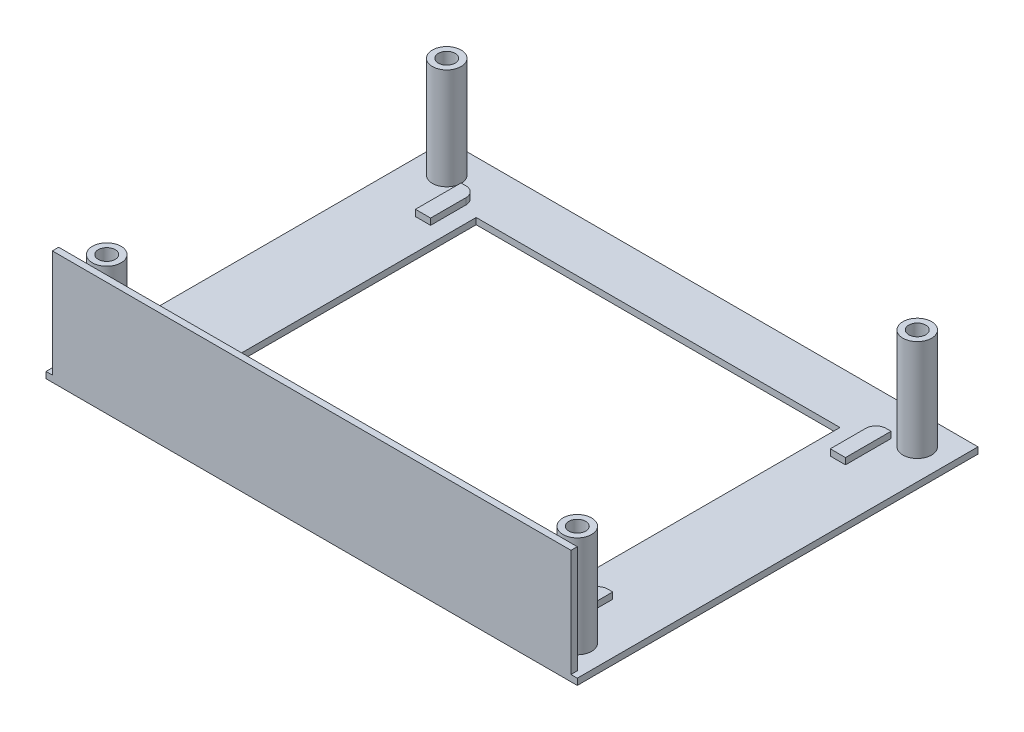
SolidWorks part; units mm, degrees
ref_plane "Front Plane" through (0, 0, 0) normal (0, 0, 1) x (1, 0, 0)
ref_plane "Top Plane" through (0, 0, 0) normal (0, 1, 0) x (1, 0, 0)
ref_plane "Right Plane" through (0, 0, 0) normal (1, 0, 0) x (0, 0, -1)
sketch "Sketch1" plane through (0, 0, 0) normal (0, 1, 0) x (1, 0, 0)
  line L1 (-45.6406, -34.1312) -> (45.6406, -34.1312)
  line L2 (-45.6406, -34.1312) -> (-45.6406, 34.1313)
  line L3 (-45.6406, 34.1313) -> (45.6406, 34.1313)
  line L4 (45.6406, -34.1312) -> (45.6406, 34.1313)
  line L5 (-45.6406, -34.1312) -> (45.6406, 34.1313) construction
  line L6 (-45.6406, 34.1313) -> (45.6406, -34.1312) construction
  line L7 (-49.6406, 38.1313) -> (50.6406, 38.1313)
  line L8 (-49.6406, 35.5913) -> (-49.6406, -43.1312)
  line L9 (-49.6406, -43.1312) -> (50.6406, -43.1312)
  line L10 (50.6406, -34.2413) -> (50.6406, -43.1312)
  line L11 (19.6844, -43.1312) -> (-7.5719, -43.1312)
  line L12 (19.6844, -43.1312) -> (19.6844, -49.4812)
  line L13 (19.6844, -49.4812) -> (-7.5719, -49.4812)
  line L14 (-7.5719, -43.1312) -> (-7.5719, -49.4812)
  line L15 (-66.1506, 47.2512) -> (67.1506, 47.2512)
  line L16 (-66.1506, 47.2512) -> (-66.1506, -53.2912)
  line L17 (-66.1506, -53.2912) -> (67.1506, -53.2912)
  line L18 (67.1506, 47.2512) -> (67.1506, -53.2912)
  line L19 (-52.1806, 38.1313) -> (-53.4506, 38.1313)
  line L20 (-49.6406, 38.1313) -> (-49.6406, 26.7013)
  line L21 (-49.6406, 26.7013) -> (-53.4506, 26.7013)
  line L22 (-53.4506, 38.1313) -> (-53.4506, 26.7013)
  line L23 (53.1806, 38.1313) -> (54.4506, 38.1313)
  line L24 (50.6406, 38.1313) -> (50.6406, 26.7013)
  line L25 (50.6406, 26.7013) -> (54.4506, 26.7013)
  line L26 (54.4506, 38.1313) -> (54.4506, 26.7013)
  line L27 (-49.6406, -43.1312) -> (-53.4506, -43.1312)
  line L28 (-49.6406, -43.1312) -> (-49.6406, -34.2413)
  line L29 (-52.1806, -31.7012) -> (-53.4506, -31.7012)
  line L30 (-53.4506, -43.1312) -> (-53.4506, -31.7012)
  line L31 (50.6406, -43.1312) -> (54.4506, -43.1312)
  line L32 (50.6406, -43.1312) -> (50.6406, -31.7012)
  line L33 (53.1806, -31.7012) -> (54.4506, -31.7012)
  line L34 (54.4506, -43.1312) -> (54.4506, -31.7012)
  line L35 (-53.4506, -46.9412) -> (-36.9406, -46.9412)
  line L36 (-53.4506, -46.9412) -> (-53.4506, -43.1312)
  line L37 (-53.4506, -43.1312) -> (-36.9406, -43.1312)
  line L38 (-36.9406, -46.9412) -> (-36.9406, -43.1312)
  line L39 (54.4506, -43.1312) -> (39.2106, -43.1312)
  line L40 (54.4506, -43.1312) -> (54.4506, -46.9412)
  line L41 (54.4506, -46.9412) -> (39.2106, -46.9412)
  line L42 (39.2106, -43.1312) -> (39.2106, -46.9412)
  line L43 (-66.1506, -53.2912) -> (67.1506, -53.2912)
  line L44 (-66.1506, -53.2912) -> (-66.1506, -51.7038)
  line L45 (-66.1506, -51.7038) -> (67.1506, -51.7038)
  line L46 (67.1506, -53.2912) -> (67.1506, -51.7038)
  line L47 (-66.1506, -51.7038) -> (-64.5631, -51.7038)
  line L48 (-66.1506, -51.7038) -> (-66.1506, -53.2912)
  line L49 (-66.1506, -53.2912) -> (-64.5631, -53.2913)
  line L50 (-64.5631, -51.7038) -> (-64.5631, -53.2913)
  line L51 (67.1506, -51.7038) -> (65.5631, -51.7038)
  line L52 (67.1506, -51.7038) -> (67.1506, -53.2912)
  line L53 (67.1506, -53.2912) -> (65.5631, -53.2913)
  line L54 (65.5631, -51.7038) -> (65.5631, -53.2913)
  arc A0 (-49.6406, 35.5913) -> (-52.1806, 38.1313) centre (-52.1806, 35.5913) ccw
  arc A1 (50.6406, 35.5912) -> (53.1806, 38.1313) centre (53.1806, 35.5913) cw
  arc A2 (50.6406, -34.2413) -> (53.1806, -31.7012) centre (53.1806, -34.2412) cw
  arc A3 (-49.6406, -34.2413) -> (-52.1806, -31.7012) centre (-52.1806, -34.2412) ccw
  circle A4 centre (59.5306, 39.6312) radius 3.6
  circle A5 centre (-58.5306, 39.6312) radius 3.6
  circle A6 centre (59.5306, -45.6712) radius 3.6
  circle A7 centre (-58.5306, -45.6713) radius 3.6
  circle A8 centre (-58.5306, 39.6312) radius 2.125
  circle A9 centre (59.5306, 39.6312) radius 2.125
  circle A10 centre (59.5306, -45.6712) radius 2.125
  circle A11 centre (-58.5306, -45.6713) radius 2.125
  point P0 (0, 0)
  point P14 (0, 0)
  point P48 (-49.6406, -31.7012)
  dimension "D24" = 2.54
  dimension "D25" = 2.54
  dimension "D20" = 2.54
  dimension "D26" = 2.54
  dimension "D27" = 7.62
  dimension "D35" = 1.5875
  dimension "D1" = 91.2812
  dimension "D2" = 68.2625
  dimension "D3" = 4
  dimension "D4" = 4
  dimension "D5" = 5
  dimension "D6" = 9
  dimension "D7" = 30.9562
  dimension "D8" = 42.0688
  dimension "D9" = 6.35
  dimension "D10" = 16.51
  dimension "D11" = 16.51
  dimension "D12" = 3.81
  dimension "D13" = 11.43
  dimension "D14" = 3.81
  dimension "D15" = 3.81
  dimension "D16" = 11.43
  dimension "D17" = 3.81
  dimension "D18" = 16.51
  dimension "D19" = 3.81
  dimension "D21" = 11.43
  dimension "D22" = 11.43
  dimension "D23" = 3.81
  dimension "D28" = 7.62
  dimension "D29" = 7.62
  dimension "D30" = 7.62
  dimension "D31" = 7.62
  dimension "D32" = 7.62
  dimension "D33" = 7.62
  dimension "D34" = 7.62
  dimension "D36" = 1.5875
  dimension "D37" = 1.5875
  dimension "D38" = 9.12
extrude "Boss-Extrude1" add sketch "Sketch1" against normal blind 1.5875 contours L17 L18 L15 L16
extrude "Boss-Extrude2" add sketch "Sketch1<3>" along normal blind 25.4 contours A5 A8 | A4 A9 | A6 A10 | A7 A11 region at (56.0324, 0, -39.6312) region at (-62.0288, 0, -39.6312) region at (56.0324, 0, 45.6712) region at (-62.0288, 0, 45.6713)
sketch "Sketch1<3>" plane through (0, 0, 0) normal (0, 1, 0) x (1, 0, 0) same geometry as "Sketch1"
extrude "Boss-Extrude4" add sketch "Sketch1<6>" along normal blind 1.5875 contours L8 A0 L19 L22 L21 | A1 L24 L25 L26 L23 | A2 L10 L31 L34 L33 | L9 L42 L41 L40 L31 | L35 L38 L9 L27 L36 | L8 A3 L29 L30 L27 region at (52.5895, 0, -32.2472) region at (46.8306, 0, 45.0362) region at (-51.5895, 0, 37.5853) region at (-51.5895, 0, -32.2472) region at (-45.1956, 0, 45.0362) region at (52.5895, 0, 37.5853)
sketch "Sketch1<6>" plane through (0, 0, 0) normal (0, 1, 0) x (1, 0, 0) same geometry as "Sketch1"
extrude "Cut-Extrude1" cut sketch "Sketch1<7>" against normal blind 4.1275 contours L1 L4 L3 L2 region at (0, 0, 0)
sketch "Sketch1<7>" plane through (0, 0, 0) normal (0, 1, 0) x (1, 0, 0) same geometry as "Sketch1"
extrude "Boss-Extrude5" add sketch "Sketch1<9>" along normal blind 26.9875 contours L54 L45 L50 L43 region at (0.5, 0, 52.4975)
sketch "Sketch1<9>" plane through (0, 0, 0) normal (0, 1, 0) x (1, 0, 0) same geometry as "Sketch1"
